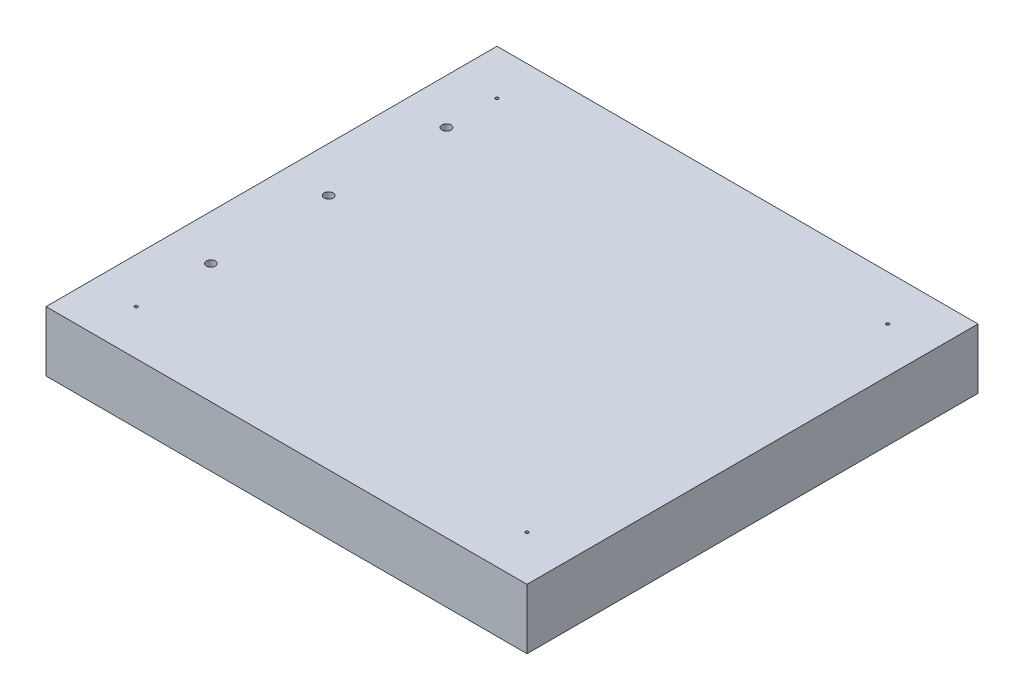
SolidWorks part; units mm, degrees
ref_plane "Plan de face" through (0, 0, 0) normal (0, 0, 1) x (1, 0, 0)
ref_plane "Plan de dessus" through (0, 0, 0) normal (0, 1, 0) x (1, 0, 0)
ref_plane "Plan de droite" through (0, 0, 0) normal (1, 0, 0) x (0, 0, -1)
sketch "Sketch2" plane through (0, 0, 0) normal (0, 1, 0) x (1, 0, 0)
  line L1 (80, -75) -> (-80, -75)
  line L2 (80, -75) -> (80, 75)
  line L3 (80, 75) -> (-80, 75)
  line L4 (-80, -75) -> (-80, 75)
  line L5 (80, -75) -> (-80, 75) construction
  line L6 (80, 75) -> (-80, -75) construction
  point P0 (0, 0)
  dimension "D1" = 150
  dimension "D2" = 160
extrude "Boss-Extrude1" add sketch "Sketch2" along normal blind 20
sketch "Sketch3" plane through (0, 20, 0) normal (0, 1, 0) x (-1, 0, 0)
  line L0 (80, -75) -> (80, 75) construction
  line L1 (-80, -75) -> (80, -75) construction
  circle A0 centre (65, -43.201) radius 1.5
  dimension "D1" = 15
  dimension "D2" = 31.799
extrude "Cut-Extrude1" cut sketch "Sketch3" against normal through all
sketch "Sketch4" plane through (0, 20, 0) normal (0, 1, 0) x (1, 0, 0)
  line L0 (-80, 75) -> (-80, -75) construction
  line L1 (80, 75) -> (-80, 75) construction
  circle A0 centre (-65, -35.161) radius 1.5
  dimension "D1" = 15
  dimension "D2" = 110.161
extrude "Cut-Extrude2" cut sketch "Sketch4" against normal through all
sketch "Sketch6" plane through (0, 20, 0) normal (0, 1, 0) x (-1, 0, 0)
  line L0 (80, -75) -> (80, 75) construction
  line L1 (-80, -75) -> (80, -75) construction
  circle A0 centre (65, -4.02) radius 1.5
  dimension "D1" = 15
  dimension "D2" = 70.98
extrude "Cut-Extrude3" cut sketch "Sketch6" against normal up to next
sketch "Sketch7" plane through (0, 20, 0) normal (0, 1, 0) x (-1, 0, 0)
  line L0 (80, -75) -> (80, 75) construction
  line L1 (-80, -75) -> (80, -75) construction
  circle A0 centre (65, -60) radius 0.5
  dimension "D1" = 15
  dimension "D2" = 15
extrude "Cut-Extrude4" cut sketch "Sketch7" against normal up to next
sketch "Sketch8" plane through (0, 20, 0) normal (0, 1, 0) x (-1, 0, 0)
  line L0 (-80, -75) -> (80, -75) construction
  line L1 (-80, 75) -> (-80, -75) construction
  circle A0 centre (-65, -60) radius 0.5
  dimension "D1" = 15
  dimension "D2" = 15
extrude "Cut-Extrude5" cut sketch "Sketch8" against normal up to next
sketch "Sketch9" plane through (0, 20, 0) normal (0, 1, 0) x (-1, 0, 0)
  line L0 (80, -75) -> (80, 75) construction
  line L1 (80, 75) -> (-80, 75) construction
  circle A0 centre (65, 60) radius 0.5
  dimension "D1" = 15
  dimension "D2" = 15
extrude "Cut-Extrude6" cut sketch "Sketch9" against normal up to next
sketch "Sketch10" plane through (0, 20, 0) normal (0, 1, 0) x (-1, 0, 0)
  line L0 (80, 75) -> (-80, 75) construction
  line L1 (-80, 75) -> (-80, -75) construction
  circle A0 centre (-65, 60) radius 0.5
  dimension "D1" = 15
  dimension "D2" = 15
extrude "Cut-Extrude7" cut sketch "Sketch10" against normal up to next
